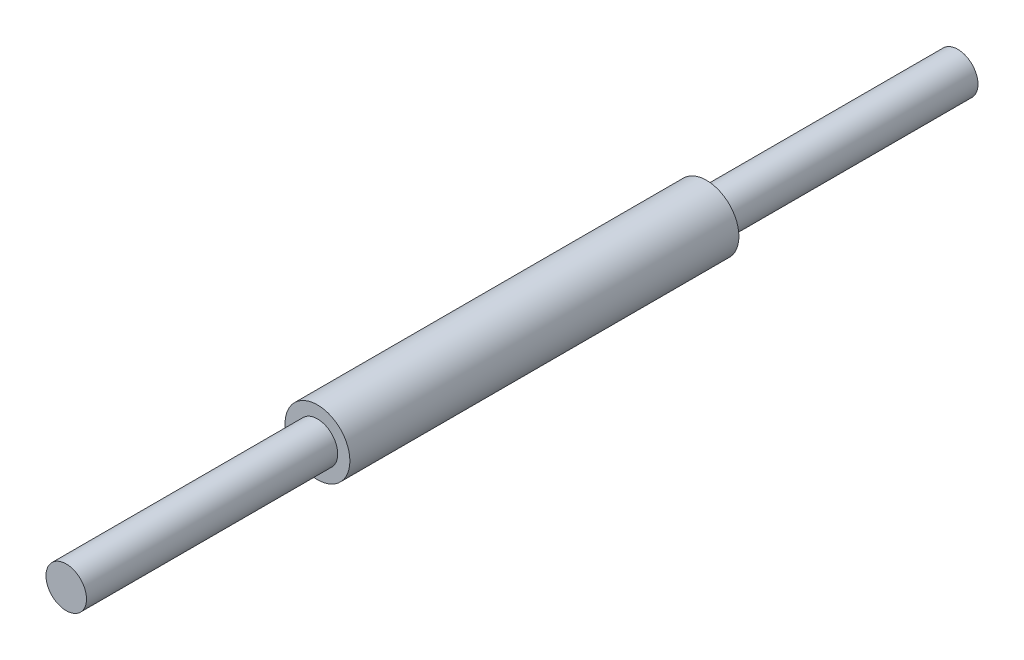
SolidWorks part; units mm, degrees
ref_plane "Front Plane" through (0, 0, 0) normal (0, 0, 1) x (1, 0, 0)
ref_plane "Top Plane" through (0, 0, 0) normal (0, 1, 0) x (1, 0, 0)
ref_plane "Right Plane" through (0, 0, 0) normal (1, 0, 0) x (0, 0, -1)
sketch "Sketch2" plane through (0, 0, 0) normal (0, 0, 1) x (1, 0, 0)
  circle A0 centre (0, 0) radius 3.175
  dimension "D1" = 6.35
extrude "Boss-Extrude1" add sketch "Sketch2" along normal blind 69.85 and the other way blind 69.85
sketch "Sketch3" plane through (0, 0, 0) normal (0, 0, 1) x (1, 0, 0)
  circle A0 centre (0, 0) radius 5.08
  dimension "D1" = 10.16
extrude "Boss-Extrude2" add sketch "Sketch3" along normal blind 30.48 and the other way blind 30.48
